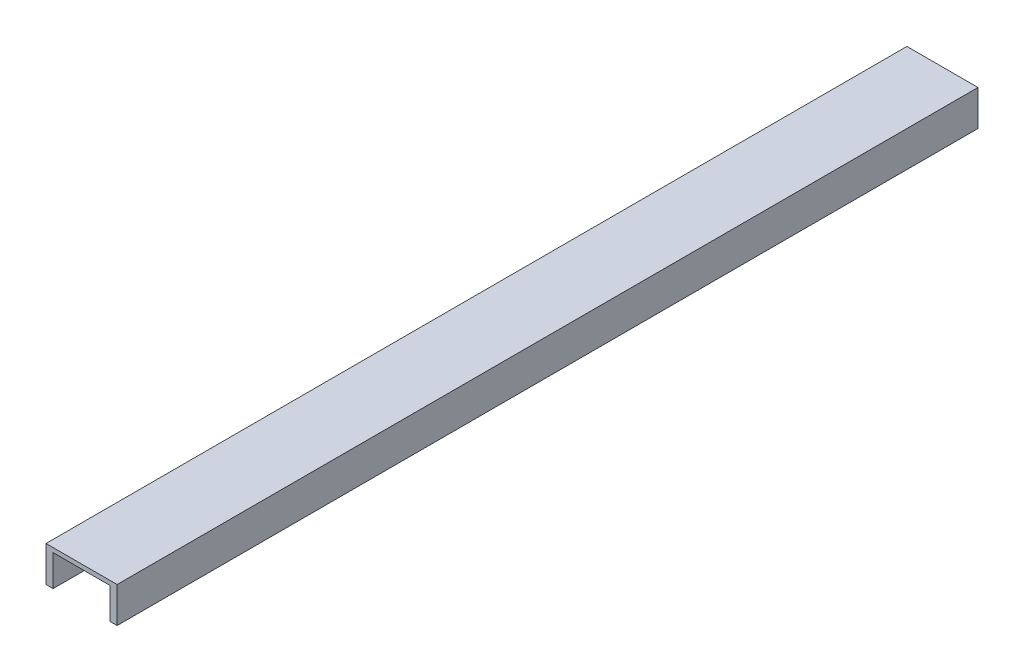
SolidWorks part; units mm, degrees
material "AISI 4340 Acero normalizado"
ref_plane "Alzado" through (0, 0, 0) normal (0, 0, 1) x (1, 0, 0)
ref_plane "Planta" through (0, 0, 0) normal (0, 1, 0) x (1, 0, 0)
ref_plane "Vista lateral" through (0, 0, 0) normal (1, 0, 0) x (0, 0, -1)
sketch "Croquis1" plane through (0, 0, 0) normal (0, 0, 1) x (1, 0, 0)
  line L0 (-28, 13.2) -> (-28, -17.5)
  line L1 (-35, 17.5) -> (35, 17.5)
  line L2 (-35, 17.5) -> (-35, -17.5)
  line L3 (-35, -17.5) -> (35, -17.5)
  line L4 (35, 17.5) -> (35, -17.5)
  line L5 (-35, 17.5) -> (35, -17.5) construction
  line L6 (-35, -17.5) -> (35, 17.5) construction
  line L8 (28, 13.2) -> (28, -17.5)
  line L12 (-28, 13.2) -> (28, 13.2)
  point P0 (0, 0)
  dimension "D1" = 35
  dimension "D2" = 70
  dimension "D3" = 4.3
  dimension "D4" = 7
  dimension "D5" = 7
extrude "Saliente-Extruir1" add sketch "Croquis1" along normal mid plane 847.6 contours L8 L3 L4 L1 L2 L0 region at (-28.7826, -2.15, 0)
